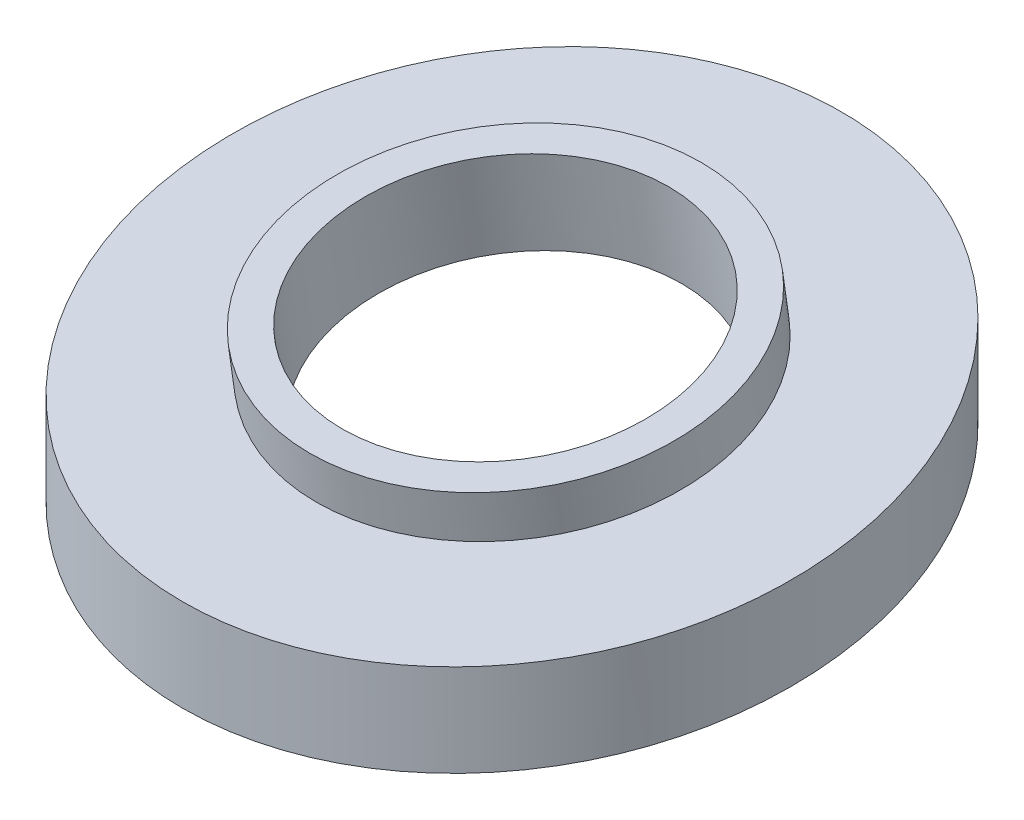
SolidWorks part; units mm, degrees
ref_plane "前视基准面" through (0, 0, 0) normal (0, 0, 1) x (1, 0, 0)
ref_plane "上视基准面" through (0, 0, 0) normal (0, 1, 0) x (1, 0, 0)
ref_plane "右视基准面" through (0, 0, 0) normal (1, 0, 0) x (0, 0, -1)
sketch "草图1" plane through (0, 0, 0) normal (0, 1, 0) x (1, 0, 0)
  circle A0 centre (0, 0) radius 25
  dimension "D1" = 50
extrude "凸台-拉伸1" add sketch "草图1" along normal blind 30
sketch "草图3" plane through (0, 0, 0) normal (1, 0, 0) x (0, 0, -1)
  line L0 (-25, 7) -> (25, 14.1889)
  line L1 (-25, 30) -> (-25, 0) construction
  line L2 (25, 0) -> (25, 30) construction
  line L3 (25, 14.1889) -> (25, 39.51)
  line L4 (25, 39.51) -> (-25, 39.51)
  line L5 (-25, 39.51) -> (-25, 7)
  line L6 (-25, 0) -> (25, 0) construction
  line L7 (0, 0) -> (0, 30.0856) construction
  line L12 (-25, 0) -> (25, 7.1889)
  line L13 (25, 0) -> (25, 30) construction
  line L14 (25, 7.1889) -> (25, -11.5725)
  line L15 (25, -11.5725) -> (-25, -11.5725)
  line L16 (-25, -11.5725) -> (-25, 0)
  line L17 (-20.2882, -2.8585) -> (21.2844, 3.1187) construction
  line L18 (-20.2882, -2.8585) -> (-21.2844, 4.0702) construction
  line L19 (21.2844, 3.1187) -> (20.2882, 10.0474) construction
  line L20 (-21.2844, 4.0702) -> (20.2882, 10.0474) construction
  line L21 (-20.2882, -2.8585) -> (20.2882, 10.0474) construction
  line L22 (21.2844, 3.1187) -> (-21.2844, 4.0702) construction
  point P21 (0, 3.5944)
  dimension "D1" = 7
  dimension "D2" = 8.182
  dimension "D3" = 42
  dimension "D4" = 0
  dimension "D5" = 7
  dimension "D6" = 3.4288
extrude "切除-拉伸1" cut sketch "草图3" against normal mid plane 63
sketch "草图10" plane through (0, 10.3799, 1.4924) normal (0, 0.9898, 0.1423) x (1, 0, 0)
  circle A0 centre (0, 1.5077) radius 15
  ellipse E0 centre (0, 1.5077) end of major axis (0, -23.7493) minor radius 25 construction
  dimension "D1" = 30
extrude "凸台-拉伸2" add sketch "草图10" along normal blind 3.5
sketch "草图11" plane through (0, 3.5216, 0.5063) normal (0, -0.9898, -0.1423) x (1, 0, 0)
  line L0 (-25, -0.5115) -> (25, -0.5115) construction
  circle A0 centre (0, -1.5077) radius 21
  circle A6 centre (0, -1.5077) radius 15 construction
  point P3 (-1.1382, 0)
  dimension "D1" = 42
  dimension "D2" = 0.9962
extrude "切除-拉伸8" cut sketch "草图11" against normal blind 3.5
sketch "草图12" plane through (0, 13.8443, 1.9905) normal (0, 0.9898, 0.1423) x (1, 0, 0)
  circle A2 centre (0, 1.5077) radius 12.5
  dimension "D1" = 25
extrude "切除-拉伸9" cut sketch "草图12" against normal blind 23.5
